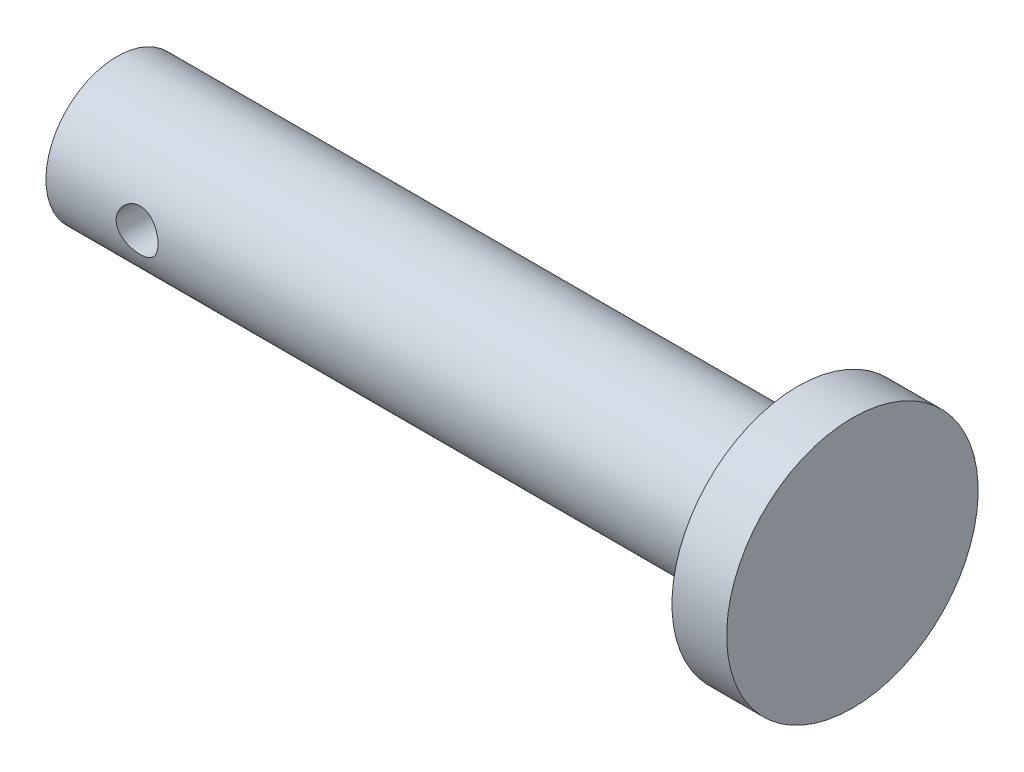
SolidWorks part; units mm, degrees
material "ABS"
ref_plane "Front Plane" through (0, 0, 0) normal (0, 0, 1) x (1, 0, 0)
ref_plane "Top Plane" through (0, 0, 0) normal (0, 1, 0) x (1, 0, 0)
ref_plane "Right Plane" through (0, 0, 0) normal (1, 0, 0) x (0, 0, -1)
sketch "Sketch2" plane through (0, 0, 0) normal (0, 0, 1) x (1, 0, 0)
  line L0 (0, 0) -> (0, -3.9) construction
  line L5 (-18.675, 0) -> (18.675, 0)
  line L6 (-18.675, 0) -> (-18.675, -3.9)
  line L7 (-18.675, -3.9) -> (18.675, -3.9)
  line L8 (18.675, 0) -> (18.675, -3.9)
  line L9 (-13.675, 0) -> (-13.675, 1.15) construction
  circle A0 centre (-13.675, 0) radius 1.15
  dimension "D1" = 32.35
  dimension "D2" = 3.9
  dimension "D3" = 1.15
  dimension "D4" = 5
revolve "Revolve2" add sketch "Sketch2" angle 360 about L5 region at (0.1978, -1.9712, 0)
extrude "Cut-Extrude1" cut sketch "Sketch2<3>" against normal through all both and the other way through all contours A0
sketch "Sketch2<3>" plane through (0, 0, 0) normal (0, 0, 1) x (1, 0, 0) same geometry as "Sketch2"
sketch "Sketch3" plane through (18.675, 0, 0) normal (1, 0, 0) x (0, 0, -1)
  line L0 (3.9, 0) -> (6.9, 0) construction
  circle A0 centre (0, 0) radius 6.9
  circle A1 centre (0, 0) radius 3.9 construction
  dimension "D1" = 3
extrude "Boss-Extrude1" add sketch "Sketch3" along normal blind 3
